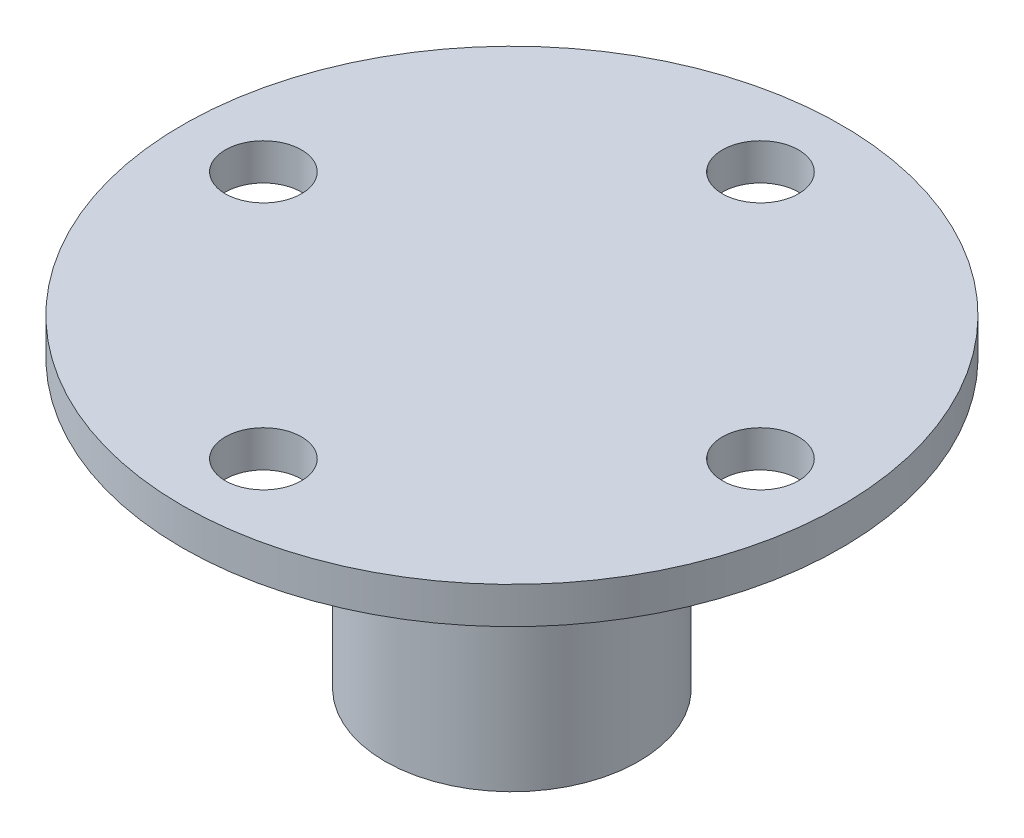
SolidWorks part; units mm, degrees
ref_plane "Front Plane" through (0, 0, 0) normal (0, 0, 1) x (1, 0, 0)
ref_plane "Top Plane" through (0, 0, 0) normal (0, 1, 0) x (1, 0, 0)
ref_plane "Right Plane" through (0, 0, 0) normal (1, 0, 0) x (0, 0, -1)
sketch "Sketch1" plane through (0, 0, 0) normal (0, 1, 0) x (1, 0, 0)
  line L0 (0, 0) -> (21.548, 0)
  line L6 (-6.7175, -3.8891) -> (-3.8891, -6.7175)
  line L7 (-3.8891, -6.7175) -> (-2.5858, -5.4142)
  line L8 (-6.7175, -3.8891) -> (-5.4142, -2.5858)
  circle A0 centre (0, 0) radius 28.575
  circle A1 centre (0, 0) radius 11
  circle A2 centre (21.548, 0) radius 3.302
  circle A3 centre (0, 0) radius 6
  circle A4 centre (0, -21.548) radius 3.302
  circle A5 centre (-21.548, 0) radius 3.302
  circle A6 centre (0, 21.548) radius 3.302
  point P20 (0, 0)
  dimension "D1" = 6.604
  dimension "D2" = 4
  dimension "D3" = 12
  dimension "D4" = 4
extrude "Boss-Extrude1" add sketch "Sketch1" along normal blind 3.175 contours A0 A6 A5 A4 A2 A1 region at (-27.7668, 0, 0)
extrude "Boss-Extrude2" add sketch "Sketch1<4>" along normal blind 3.175 contours A3 | A3 L8 L6 L7 | A3 A1 L7 L6 L8 region at (-10.6889, 0, 0) region at (3.1099, 0, 4.9316) region at (-4.7307, 0, 4.7307)
sketch "Sketch1<4>" plane through (0, 0, 0) normal (0, 1, 0) x (1, 0, 0) same geometry as "Sketch1"
extrude "Boss-Extrude3" add sketch "Sketch1<5>" against normal blind 24.825 contours A3 A1 L7 L6 L8 region at (-10.6889, 0, 0)
sketch "Sketch1<5>" plane through (0, 0, 0) normal (0, 1, 0) x (1, 0, 0) same geometry as "Sketch1"
